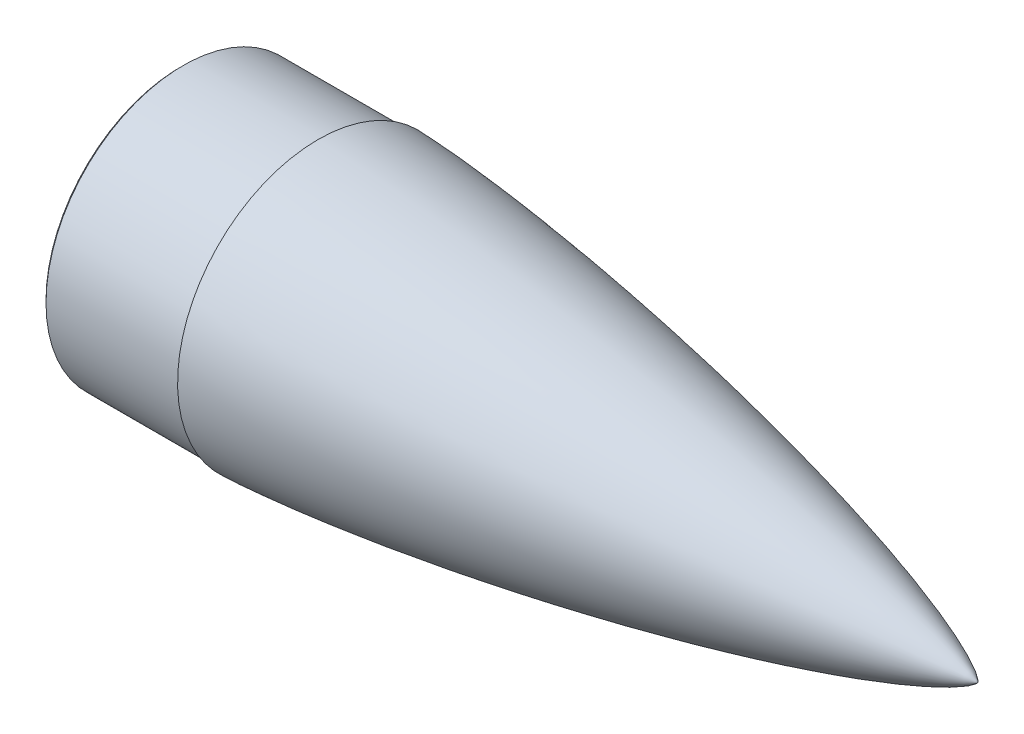
SolidWorks part; units mm, degrees
material "Plain Carbon Steel"
ref_plane "Front Plane" through (0, 0, 0) normal (0, 0, 1) x (1, 0, 0)
ref_plane "Top Plane" through (0, 0, 0) normal (0, 1, 0) x (1, 0, 0)
ref_plane "Right Plane" through (0, 0, 0) normal (1, 0, 0) x (0, 0, -1)
ref_axis "Axis1" through (46.9179, 0, 0) along (-1, 0, 0)
sketch "Sketch10" plane through (0, 0, 0) normal (0, 0, 1) x (1, 0, 0)
  line L1 (-1.0327, 0) -> (486.9547, 0) construction
  line L2 (11.1125, 81.9998) -> (11.1125, 67.4998)
  line L3 (11.1125, 81.9998) -> (-84.6045, 81.9998)
  line L4 (408.9673, 0) -> (368.9673, 0)
  line L5 (-84.6045, 81.9998) -> (-84.6045, 84.9998)
  line L6 (-84.6045, 84.9998) -> (0.3953, 84.9998)
  line L7 (0.3953, 84.9998) -> (0.3953, 86.9998)
  line L8 (11.1125, 67.4998) -> (129.3045, 67.4998)
  spline S0 degree 4 poles (408.9673, 0) (408.9649, 0.0135) (408.958, 0.0399) (408.9365, 0.0905) (408.8922, 0.1741) (408.8263, 0.2756) (408.7217, 0.4158) (408.5611, 0.6051) (408.3056, 0.8724) (407.8697, 1.2753) (407.121, 1.8851) (405.8038, 2.8259) (403.4624, 4.2872) (399.3253, 6.5318) (392.4811, 9.7589) (380.6621, 14.628) (363.6372, 20.7117) (342.2152, 27.4765) (317.4285, 34.4976) (291.8793, 41.1048) (266.2105, 47.229) (240.4455, 52.9334) (214.5989, 58.2554) (188.6809, 63.2176) (165.9462, 67.2533) (146.422, 70.4938) (130.1279, 73.0449) (117.0786, 74.9942) (104.0155, 76.8485) (92.5733, 78.3845) (82.7571, 79.6356) (74.5713, 80.6322) (68.0193, 81.4008) (61.4637, 82.1394) (54.9047, 82.8464) (48.3422, 83.5199) (41.7761, 84.1578) (36.0275, 84.6822) (31.0979, 85.1052) (26.9883, 85.4387) (23.6997, 85.6932) (20.0858, 85.9584) (16.7199, 86.189) (13.6021, 86.387) (10.7327, 86.5546) (8.4366, 86.6787) (6.14, 86.7922) (4.1299, 86.8793) (2.4065, 86.9446) (1.2573, 86.979) (0.6827, 86.9949) (0.3953, 86.9998) knots 0 0 0 0 0 0.00013 0.00026 0.00052 0.0009 0.00128 0.001925 0.002882 0.004418 0.006927 0.011111 0.018279 0.030673 0.051704 0.083102 0.139909 0.202703 0.265496 0.32829 0.391083 0.453877 0.516671 0.579464 0.642258 0.673655 0.705051 0.736448 0.767845 0.799242 0.81494 0.830639 0.846337 0.862036 0.877734 0.893432 0.909131 0.924829 0.932678 0.940527 0.948377 0.956226 0.967169 0.972641 0.978113 0.983585 0.989056 0.994528 0.997264 1 1 1 1 1 construction
  spline S1 degree 4 poles (408.9673, 0) (408.9649, 0.0135) (408.958, 0.0399) (408.9365, 0.0905) (408.8922, 0.1741) (408.8263, 0.2756) (408.7217, 0.4158) (408.5611, 0.6051) (408.3056, 0.8724) (407.8697, 1.2753) (407.121, 1.8851) (405.8038, 2.8259) (403.4624, 4.2872) (399.3253, 6.5318) (392.4811, 9.7589) (380.6621, 14.628) (363.6372, 20.7117) (342.2152, 27.4765) (317.4285, 34.4976) (291.8793, 41.1048) (266.2105, 47.229) (240.4455, 52.9334) (214.5989, 58.2554) (188.6809, 63.2176) (165.9462, 67.2533) (146.422, 70.4938) (130.1279, 73.0449) (117.0786, 74.9942) (104.0155, 76.8485) (92.5733, 78.3845) (82.7571, 79.6356) (74.5713, 80.6322) (68.0193, 81.4008) (61.4637, 82.1394) (54.9047, 82.8464) (48.3422, 83.5199) (41.7761, 84.1578) (36.0275, 84.6822) (31.0979, 85.1052) (26.9883, 85.4387) (23.6997, 85.6932) (20.0858, 85.9584) (16.7199, 86.189) (13.6021, 86.387) (10.7327, 86.5546) (8.4366, 86.6787) (6.14, 86.7922) (4.1299, 86.8793) (2.4065, 86.9446) (1.2573, 86.979) (0.6827, 86.9949) (0.3953, 86.9998) knots 0 0 0 0 0 0.00013 0.00026 0.00052 0.0009 0.00128 0.001925 0.002882 0.004418 0.006927 0.011111 0.018279 0.030673 0.051704 0.083102 0.139909 0.202703 0.265496 0.32829 0.391083 0.453877 0.516671 0.579464 0.642258 0.673655 0.705051 0.736448 0.767845 0.799242 0.81494 0.830639 0.846337 0.862036 0.877734 0.893432 0.909131 0.924829 0.932678 0.940527 0.948377 0.956226 0.967169 0.972641 0.978113 0.983585 0.989056 0.994528 0.997264 1 1 1 1 1
  spline S2 degree 4 poles (368.9673, 0) (368.9653, 0.0123) (368.9594, 0.0365) (368.9406, 0.083) (368.9023, 0.1587) (368.8455, 0.2503) (368.7557, 0.3766) (368.6167, 0.5484) (368.3929, 0.7936) (368.0087, 1.1649) (367.3447, 1.7299) (366.1761, 2.6016) (364.0928, 3.96) (360.426, 6.0407) (354.4022, 9.0183) (344.043, 13.5077) (329.152, 19.1285) (310.4252, 25.3986) (288.7413, 31.9337) (266.3785, 38.1061) (243.9014, 43.8469) (221.332, 49.212) (198.684, 54.2345) (175.9669, 58.9343) (156.0346, 62.7717) (138.9133, 65.8645) (124.6221, 68.3077) (113.1754, 70.1797) (101.7151, 71.9664) (91.6754, 73.4517) (83.0615, 74.6659) (75.8775, 75.6363) (70.1269, 76.3867) (64.3728, 77.1101) (58.6152, 77.8049) (52.854, 78.4695) (47.0892, 79.1019) (42.0417, 79.6247) (37.7129, 80.0488) (34.1039, 80.385) (31.2157, 80.6428) (28.0648, 80.911) (24.6507, 81.1843) (21.4654, 81.4195) (18.5093, 81.6177) (16.0448, 81.767) (14.3191, 81.8612) (12.8395, 81.9336) (11.8527, 81.9739) (11.3593, 81.993) (11.1125, 81.9998) knots 0 0 0 0 0 0.000135 0.00027 0.00054 0.00092 0.001299 0.001947 0.002931 0.004512 0.007081 0.01138 0.018708 0.031424 0.052705 0.084103 0.14091 0.203703 0.266497 0.329291 0.392084 0.454878 0.517672 0.580465 0.643259 0.674656 0.706052 0.737449 0.768846 0.800243 0.815941 0.831639 0.847338 0.863036 0.878735 0.894433 0.910132 0.92583 0.933679 0.941528 0.949378 0.957227 0.96792 0.978613 0.98396 0.989307 0.994653 0.997327 1 1 1 1 1 construction
  spline S3 degree 4 poles (368.9673, 0) (368.9653, 0.0123) (368.9594, 0.0365) (368.9406, 0.083) (368.9023, 0.1587) (368.8455, 0.2503) (368.7557, 0.3766) (368.6167, 0.5484) (368.3929, 0.7936) (368.0087, 1.1649) (367.3447, 1.7299) (366.1761, 2.6016) (364.0928, 3.96) (360.426, 6.0407) (354.4022, 9.0183) (344.043, 13.5077) (329.152, 19.1285) (310.4252, 25.3986) (288.7413, 31.9337) (266.3785, 38.1061) (243.9014, 43.8469) (221.332, 49.212) (198.684, 54.2345) (175.9669, 58.9343) (156.0346, 62.7717) (141.5091, 65.3956) (132.6794, 66.9245) (129.5628, 67.4559) (129.3045, 67.4998) knots 0 0 0 0 0 0.000135 0.00027 0.00054 0.00092 0.001299 0.001947 0.002931 0.004512 0.007081 0.01138 0.018708 0.031424 0.052705 0.084103 0.14091 0.203703 0.266497 0.329291 0.392084 0.454878 0.517672 0.580465 0.643259 0.674656 0.677492 0.677492 0.677492 0.677492 0.677492
  dimension "D1" = 86.9998
  dimension "D2" = 3
  dimension "D3" = 410
  dimension "D4" = 84.9998
  dimension "D5" = 370
  dimension "D6" = 84.9998
  dimension "D7" = 19.5
  dimension "D8" = 118.192
revolve "Revolve1" add sketch "Sketch10" angle 360 about axis through (46.9179, 0, 0) along (-1, 0, 0)
chamfer "Chamfer1" distance 1.5 angle 45 1 edges at (-84.6045, 0, -84.9998)
ref_plane "Plane1" through (70, 0, 0) normal (1, 0, 0) x (0, 0, -1)
sketch "Sketch11" plane through (70, 0, 0) normal (1, 0, 0) x (0, 0, -1)
  line L0 (39.6458, -13.0184) -> (39.6458, 13.0184)
  line L1 (-13.0184, -39.6458) -> (-13.0184, -66.2327)
  line L2 (-13.0184, -39.6458) -> (13.0184, -39.6458)
  line L3 (39.6458, -13.0184) -> (66.2327, -13.0184)
  line L4 (39.6458, 13.0184) -> (66.2327, 13.0184)
  line L5 (13.0184, -39.6458) -> (13.0184, -66.2327)
  line L6 (-39.6458, 13.0184) -> (-66.2327, 13.0184)
  line L7 (-39.6458, 13.0184) -> (-39.6458, -13.0184)
  line L8 (-39.6458, -13.0184) -> (-66.2327, -13.0184)
  line L9 (13.0184, 39.6458) -> (13.0184, 66.2327)
  line L10 (13.0184, 39.6458) -> (-13.0184, 39.6458)
  line L11 (-13.0184, 39.6458) -> (-13.0184, 66.2327)
  circle A0 centre (0, 0) radius 67.5
  circle A1 centre (0, 0) radius 67.5
  circle A2 centre (0, 0) radius 67.5
  circle A3 centre (0, 0) radius 67.5
  circle A4 centre (0, 52.1458) radius 2.5
  circle A5 centre (0, 0) radius 67.5
  circle A6 centre (52.1458, 0) radius 2.5
  circle A7 centre (0, 0) radius 67.5
  circle A8 centre (0, -52.1458) radius 2.5
  circle A9 centre (0, 0) radius 67.5
  circle A10 centre (-52.1458, 0) radius 2.5
  point P26 (0, 0)
  point P39 (0, 0)
  dimension "D1" = 4
  dimension "D2" = 4
extrude "Boss-Extrude6" add sketch "Sketch11" along normal blind 7.5 and the other way blind 7.5 contours L9 A0 L11 L10 | L3 A0 L4 L0 | L1 A0 L5 L2 | L6 A0 L8 L7 region at (70, 0, -40.027) region at (70, -67.1187, 0) region at (70, 52.9392, -12.6371) region at (70, 0, 67.1187)
